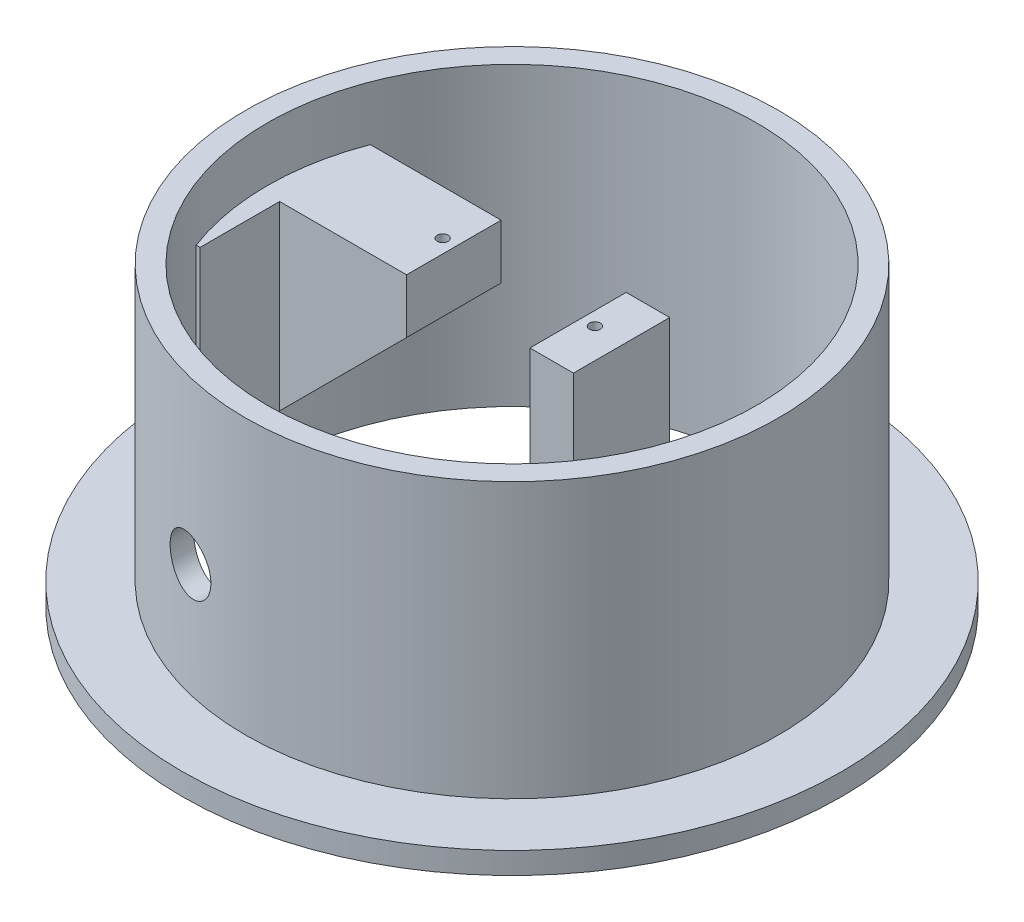
SolidWorks part; units mm, degrees
ref_plane "Front Plane" through (0, 0, 0) normal (0, 0, 1) x (1, 0, 0)
ref_plane "Top Plane" through (0, 0, 0) normal (0, 1, 0) x (1, 0, 0)
ref_plane "Right Plane" through (0, 0, 0) normal (1, 0, 0) x (0, 0, -1)
sketch "Sketch1" plane through (0, 0, 0) normal (0, 1, 0) x (1, 0, 0)
  circle A0 centre (0, 0) radius 60.625
  circle A1 centre (0, 0) radius 45
  dimension "D1" = 121.25
  dimension "D2" = 90
extrude "Boss-Extrude1" add sketch "Sketch1" along normal blind 4
sketch "Sketch2" plane through (0, 4, 0) normal (0, 1, 0) x (1, 0, 0)
  circle A0 centre (0, 0) radius 45 construction
  circle A1 centre (0, 0) radius 45
  circle A2 centre (0, 0) radius 49
  dimension "D1" = 4
extrude "Boss-Extrude2" add sketch "Sketch2" along normal blind 50.5
ref_plane "Plane1" through (0, 34.5, 0) normal (0, 1, 0) x (1, 0, 0)
sketch "Sketch4" plane through (0, 0, 0) normal (0, 0, 1) x (1, 0, 0)
  line L0 (-60.625, 0) -> (60.625, 0) construction
  line L1 (5, 44.5) -> (13, 44.5)
  line L2 (5, 44.5) -> (5, 0)
  line L3 (5, 0) -> (13, 0)
  line L4 (13, 44.5) -> (13, 0)
  line L5 (49, 54.5) -> (-49, 54.5) construction
  line L6 (-45, 54.5) -> (-45, 4)
  line L7 (-18, 44.5) -> (-45, 44.5)
  line L8 (-18, 44.5) -> (-18, 34.5)
  line L9 (-18, 34.5) -> (-45, 34.5)
  line L10 (-45, 44.5) -> (-45, 34.5)
  line L11 (60.625, 4) -> (-60.625, 4) construction
  line L12 (-18, 34.5) -> (-45, 7.5)
  dimension "D1" = 5
  dimension "D2" = 8
  dimension "D3" = 10
  dimension "D4" = 23
  dimension "D5" = 27
  dimension "D6" = 10
  dimension "D7" = 45
  dimension "D8" = 10
extrude "Boss-Extrude4" add sketch "Sketch4" along normal mid plane 32 contours L9 L8 L7 L6 | L12 L9 L6 | L1 L4 L3 L2 region at (-31.5, 39.5, 0) region at (-36, 25.5, 0)
sketch "Sketch5" plane through (0, 0, 0.8324) normal (0, -1, 0) x (1, 0, 0)
  line L0 (0.9227, 14.5796) -> (36.1058, 30.1379)
  line L1 (0.9227, -16.0291) -> (36.6512, -32.9046)
  line L2 (0.9227, 14.5796) -> (0.9227, -16.0291)
  arc A1 (36.6512, -32.9046) -> (36.1058, 30.1379) centre (-2.8733, -1.7229) ccw
extrude "Boss-Extrude5" add sketch "Sketch5" against normal up to surface (4 mm away) contours L0 A1 L1 L2 up to face at (0, 4, 60.625)
sketch "Sketch6" plane through (0, 0, 0) normal (0, 0, 1) x (1, 0, 0)
  circle A0 centre (-11.8474, 24.4856) radius 5
extrude "Cut-Extrude2" cut sketch "Sketch6" along normal blind 52 contours A0
sketch "Sketch7" plane through (0, 44.5, 0) normal (0, 1, 0) x (1, 0, 0)
  line L0 (-18, -16) -> (-18, 16) construction
  line L1 (5, -16) -> (5, 16) construction
  circle A0 centre (-20.5, 7.7399) radius 1
  circle A1 centre (7.5, 7.7399) radius 1
  dimension "D1" = 2.5
  dimension "D2" = 2.5
extrude "Cut-Extrude3" cut sketch "Sketch7" against normal blind 4.5
sketch "Sketch8" plane through (0, 44.5, 0.701) normal (0, 1, 0) x (1, 0, 0)
  line L1 (5, -1) -> (13, -1)
  line L2 (5, -1) -> (5, -16)
  line L3 (5, -16) -> (13, -16)
  line L4 (13, -1) -> (13, -16)
  dimension "D1" = 8
  dimension "D2" = 15
extrude "Cut-Extrude4" cut sketch "Sketch8" against normal blind 40.5
sketch "Sketch9" plane through (0, 44.5, 0.701) normal (0, 1, 0) x (1, 0, 0)
  line L1 (-41.34, -0.6916) -> (-16.34, -0.6916)
  line L2 (-41.34, -0.6916) -> (-41.34, -16.5689)
  line L3 (-41.34, -16.5689) -> (-16.34, -16.5689)
  line L4 (-16.34, -0.6916) -> (-16.34, -16.5689)
  dimension "D1" = 25
  dimension "D2" = 15.8773
extrude "Cut-Extrude5" cut sketch "Sketch9" against normal blind 35
sketch "Sketch11" plane through (0, 4, 0) normal (0, 1, 0) x (1, 0, 0)
  line L0 (16.2655, 12.7324) -> (16.2655, -6.5497)
  line L1 (16.2655, -6.5497) -> (5.715, -6.5497)
  line L2 (5.715, -6.5497) -> (5.715, -11.643)
  line L3 (5.715, -11.643) -> (30.818, -22.5574)
  line L4 (16.2655, 12.7324) -> (32.152, 20.615)
  arc A0 (32.152, 20.615) -> (30.818, -22.5574) centre (5.8984, -0.1806) cw
extrude "Cut-Extrude6" cut sketch "Sketch11" against normal through all
